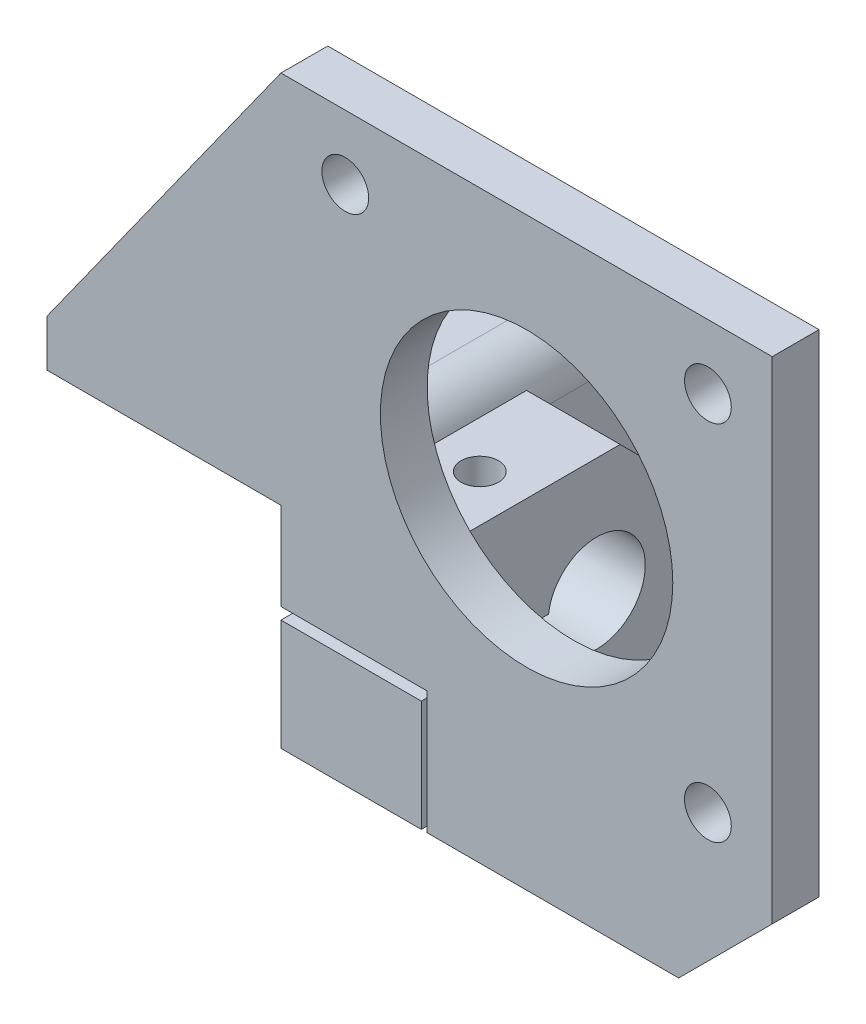
SolidWorks part; units mm, degrees
ref_plane "Plano frontal" through (0, 0, 0) normal (0, 0, 1) x (1, 0, 0)
ref_plane "Plano superior" through (0, 0, 0) normal (0, 1, 0) x (1, 0, 0)
ref_plane "Plano direito" through (0, 0, 0) normal (1, 0, 0) x (0, 0, -1)
sketch "Esboço1" plane through (0, 0, 0) normal (0, 0, 1) x (1, 0, 0)
  line L0 (-21, -11) -> (-41, -11)
  line L1 (-21, 21) -> (21, 21)
  line L2 (-21, -11) -> (-21, -21)
  line L4 (21, 21) -> (21, -21)
  line L5 (-21, 21) -> (21, -21) construction
  line L6 (-21, -21) -> (21, 21) construction
  line L7 (-15.5, 15.5) -> (15.5, 15.5) construction
  line L8 (-15.5, 15.5) -> (-15.5, -15.5) construction
  line L9 (-15.5, -15.5) -> (15.5, -15.5) construction
  line L10 (15.5, 15.5) -> (15.5, -15.5) construction
  line L11 (-15.5, 15.5) -> (15.5, -15.5) construction
  line L12 (-15.5, -15.5) -> (15.5, 15.5) construction
  line L13 (-41, -11) -> (-41, -7)
  line L14 (-21, -21) -> (-21, -29)
  line L15 (-21, -29) -> (13, -29)
  line L16 (13, -29) -> (21, -21)
  line L17 (-41, -7) -> (-21, 21)
  circle A0 centre (-15.5, 15.5) radius 2
  circle A1 centre (15.5, 15.5) radius 2
  circle A2 centre (15.5, -15.5) radius 2
  circle A3 centre (0, 0) radius 12.5
  point P0 (0, 0)
  point P6 (0, 0)
  dimension "D2" = 4
  dimension "D5" = 25
  dimension "D1" = 31
  dimension "D3" = 42
  dimension "D4" = 42
  dimension "D6" = 45
  dimension "D7" = 20
  dimension "D8" = 8
  dimension "D9" = 4
  dimension "D10" = 10
extrude "Ressalto-extrusão1" add sketch "Esboço1" along normal blind 4
sketch "Esboço2" plane through (0, 0, 0) normal (0, 0, -1) x (-1, 0, 0)
  line L0 (41, -11) -> (41, -7)
  line L1 (41, -7) -> (21, -7)
  line L2 (17, -11) -> (17, -29)
  line L3 (21, -29) -> (-13, -29) construction
  line L4 (17, -29) -> (21, -29)
  line L5 (21, -29) -> (21, -11)
  line L6 (21, -11) -> (41, -11)
  arc A0 (21, -7) -> (17, -11) centre (21, -11) ccw
  dimension "D1" = 4
extrude "Ressalto-extrusão2" add sketch "Esboço2" along normal blind 25
sketch "Esboço3" plane through (-17, 0, 0) normal (1, 0, 0) x (0, 0, -1)
  line L0 (0, -9) -> (13, -9)
  line L1 (0, -11) -> (0, -29) construction
  line L2 (13, -9) -> (18, -14)
  line L3 (18, -14) -> (18, -24)
  line L4 (18, -24) -> (13, -29)
  line L5 (25, -29) -> (0, -29) construction
  line L6 (13, -29) -> (0, -29)
  line L7 (0, -29) -> (0, -9)
  line L8 (-4, -29) -> (-4, -21) construction
  line L9 (13, -9) -> (13, -29) construction
  circle A0 centre (11, -19) radius 4.15
  point P6 (18, -19)
  dimension "D1" = 8.3
  dimension "D2" = 15
  dimension "D3" = 20
  dimension "D4" = 10
  dimension "D5" = 2
extrude "Ressalto-extrusão3" add sketch "Esboço3" along normal blind 8
sketch "Esboço4" plane through (0, 0, 0) normal (0, 0, -1) x (-1, 0, 0)
  line L0 (8.5, -18.5) -> (21.5, -18.5)
  line L3 (21.5, -18.5) -> (21.5, -26)
  line L4 (21.5, -26) -> (21, -29)
  line L5 (9, -29) -> (17, -29) construction
  line L6 (21, -29) -> (21, -19.5)
  line L7 (21, -19.5) -> (9, -19.5)
  line L8 (9, -19.5) -> (9, -29)
  line L9 (9, -29) -> (8.5, -29)
  line L10 (8.5, -29) -> (8.5, -18.5)
  dimension "D1" = 10.5
  dimension "D2" = 1
  dimension "D3" = 0.5
  dimension "D4" = 0.5
extrude "Corte-extrusão1" cut sketch "Esboço4" against normal blind 8 and the other way blind 8
sketch "Esboço5" plane through (-17, 0, 0) normal (1, 0, 0) x (0, 0, -1)
  line L0 (25, -11) -> (15, -11) construction
  line L1 (25, -29) -> (25, -11) construction
  circle A0 centre (21, -21) radius 1.75
  circle A2 centre (11, -19) radius 4.15
  dimension "D3" = 3.5
  dimension "D1" = 10
  dimension "D2" = 4
extrude "Corte-extrusão2" cut sketch "Esboço5" against normal blind 12
sketch "Esboço6" plane through (0, -7, 0) normal (0, 1, 0) x (1, 0, 0)
  line L0 (-21, 25) -> (-21, 0) construction
  line L1 (-41, 25) -> (-21, 25) construction
  circle A0 centre (-31.5, 18) radius 1.75
  circle A1 centre (-31.5, -2) radius 1.75
  dimension "D2" = 3.5
  dimension "D1" = 20
  dimension "D3" = 10.5
  dimension "D4" = 7
extrude "Corte-extrusão3" cut sketch "Esboço6" against normal blind 12
sketch "Esboço7" plane through (0, -29, 0) normal (0, -1, 0) x (1, 0, 0)
  line L0 (-9, -13) -> (-17, -13) construction
  line L2 (-8.5, 0) -> (13, 0) construction
  circle A0 centre (-13, -5) radius 1.6
  point P2 (0, 0)
  point P5 (-13, -13)
  point P6 (0, 0)
  dimension "D2" = 3.2
  dimension "D1" = 5
extrude "Corte-extrusão4" cut sketch "Esboço7" against normal through all
